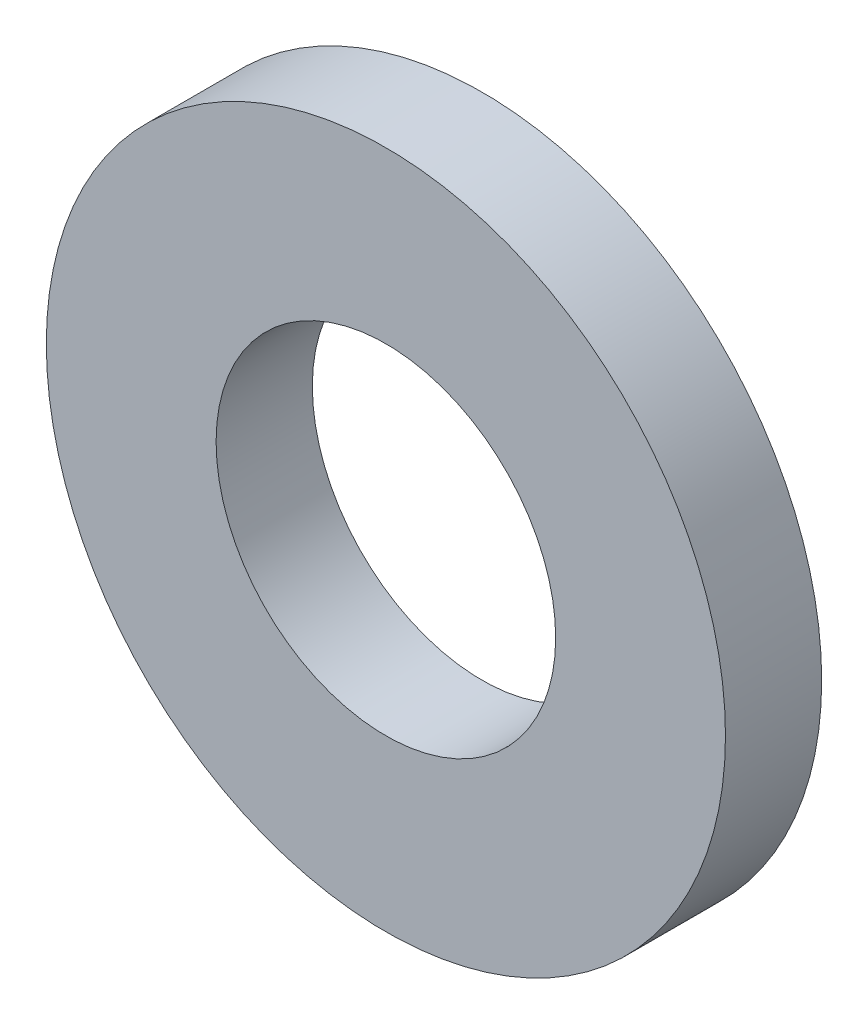
SolidWorks part; units mm, degrees
ref_plane "Front Plane" through (0, 0, 0) normal (0, 0, 1) x (1, 0, 0)
ref_plane "Top Plane" through (0, 0, 0) normal (0, 1, 0) x (1, 0, 0)
ref_plane "Right Plane" through (0, 0, 0) normal (1, 0, 0) x (0, 0, -1)
sketch "Sketch1" plane through (0, 0, 0) normal (0, 0, 1) x (1, 0, 0)
  circle A0 centre (0, 0) radius 6
  circle A1 centre (0, 0) radius 3
  dimension "OD" = 12
  dimension "ID1" = 6
extrude "Boss-Extrude1" add sketch "Sketch1" along normal blind 1.7
ref_axis "Center Axis 1" through (0, 0, 1.7) along (0, 0, -1)
ref_plane "Contact Plane 1" through (0, 0, 1.7) normal (0, 0, 1) x (1, 0, 0)
ref_plane "Contact Plane 2" through (0, 0, 0) normal (0, 0, -1) x (-1, 0, 0)
